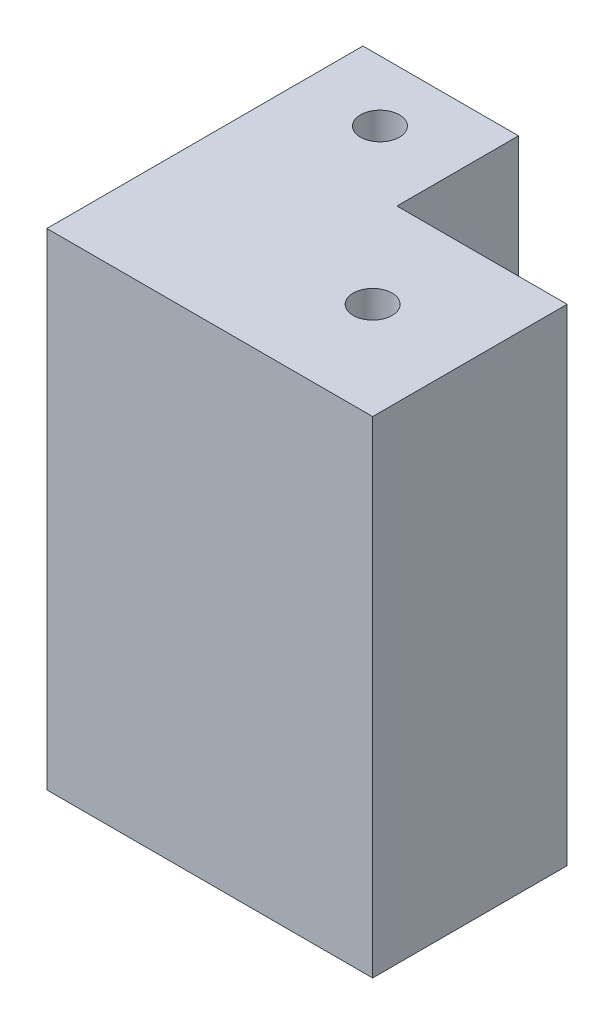
SolidWorks part; units mm, degrees
ref_plane "Front Plane" through (0, 0, 0) normal (0, 0, 1) x (1, 0, 0)
ref_plane "Top Plane" through (0, 0, 0) normal (0, 1, 0) x (1, 0, 0)
ref_plane "Right Plane" through (0, 0, 0) normal (1, 0, 0) x (0, 0, -1)
sketch "Sketch1" plane through (0, 0, 0) normal (0, 1, 0) x (1, 0, 0)
  line L0 (0, 0) -> (0, 25)
  line L1 (0, 25) -> (-32, 25)
  line L2 (-32, 25) -> (-32, -40)
  line L3 (-32, -40) -> (35, -40)
  line L4 (35, -40) -> (35, 0)
  line L5 (35, 0) -> (0, 0)
  line L6 (-32, 0) -> (0, 0) construction
  line L7 (0, -40) -> (0, 0) construction
  line L8 (0, 25) -> (-32, 0) construction
  line L9 (25, 25) -> (25, 0) construction
  line L10 (0, 25) -> (25, 25) construction
  line L11 (25, 0) -> (5, -40) construction
  line L12 (5, 5) -> (5, -40) construction
  line L13 (25, 25) -> (5, 25) construction
  line L14 (25, 25) -> (25, 5) construction
  line L15 (25, 5) -> (5, 5) construction
  line L16 (5, 25) -> (5, 5) construction
  circle A0 centre (-16, 12.5) radius 4
  circle A1 centre (15, -20) radius 4
  circle A2 centre (-16, 12.5) radius 11 construction
  circle A3 centre (-16, 12.5) radius 6 construction
  circle A4 centre (15, -20) radius 6.75 construction
  circle A5 centre (15, -20) radius 16 construction
  dimension "D4" = 8
  dimension "D5" = 22
  dimension "D6" = 12
  dimension "D7" = 13.5
  dimension "D8" = 32
  dimension "D1" = 25
  dimension "D2" = 25
  dimension "D3" = 40
  dimension "D9" = 41
  dimension "D10" = 20
  dimension "D11" = 20
extrude "Boss-Extrude1" add sketch "Sketch1" along normal blind 100
ref_plane "Plane1" through (0, 0, 0) normal (0, -1, 0) x (-1, 0, 0)
sketch "Sketch8" plane through (0, 0, 0) normal (0, -1, 0) x (-1, 0, 0)
  point P0 (-15, -20)
hole_wizard "CBORE for M5 Hex Head Bolt2" positions "Sketch8" profile "Sketch9" counterbore size "M5" standard "ANSI Metric"
sketch "Sketch9" plane through (15, 0, 20) normal (1, 0, 0) x (0, 0, -1)
  line L0 (0, 0) -> (0, 23.85)
  line L1 (0, 23.85) -> (6.75, 23.85)
  line L2 (6.75, 23.85) -> (6.75, 5)
  line L3 (6.75, 5) -> (16, 5)
  line L4 (16, 5) -> (16, 0)
  line L5 (16, 0) -> (0, 0)
  line L10 (0, 23.85) -> (-6.75, 23.85) construction
  line L11 (0, -6.35) -> (0, 107.95) construction
  dimension "Hole Dia." = 13.5
  dimension "Hole Depth" = 23.85
  dimension "C'Bore Dia." = 32
  dimension "C'Bore Depth" = 5
  dimension "Drill Angle" = 180
sketch "Sketch10" plane through (0, 0, 0) normal (0, -1, 0) x (-1, 0, 0)
  point P0 (16, 12.5)
hole_wizard "CBORE for M5 Hex Head Bolt3" positions "Sketch10" profile "Sketch11" counterbore size "M5" standard "ANSI Metric"
sketch "Sketch11" plane through (-16, 0, -12.5) normal (1, 0, 0) x (0, 0, -1)
  line L0 (0, 0) -> (0, 13.5)
  line L1 (0, 13.5) -> (5.1, 13.5)
  line L2 (5.1, 13.5) -> (5.1, 3.5)
  line L3 (5.1, 3.5) -> (11, 3.5)
  line L4 (11, 3.5) -> (11, 0)
  line L5 (11, 0) -> (0, 0)
  line L10 (0, 13.5) -> (-5.1, 13.5) construction
  line L11 (0, -6.35) -> (0, 107.95) construction
  dimension "Hole Dia." = 10.2
  dimension "Hole Depth" = 13.5
  dimension "C'Bore Dia." = 22
  dimension "C'Bore Depth" = 3.5
  dimension "Drill Angle" = 180
